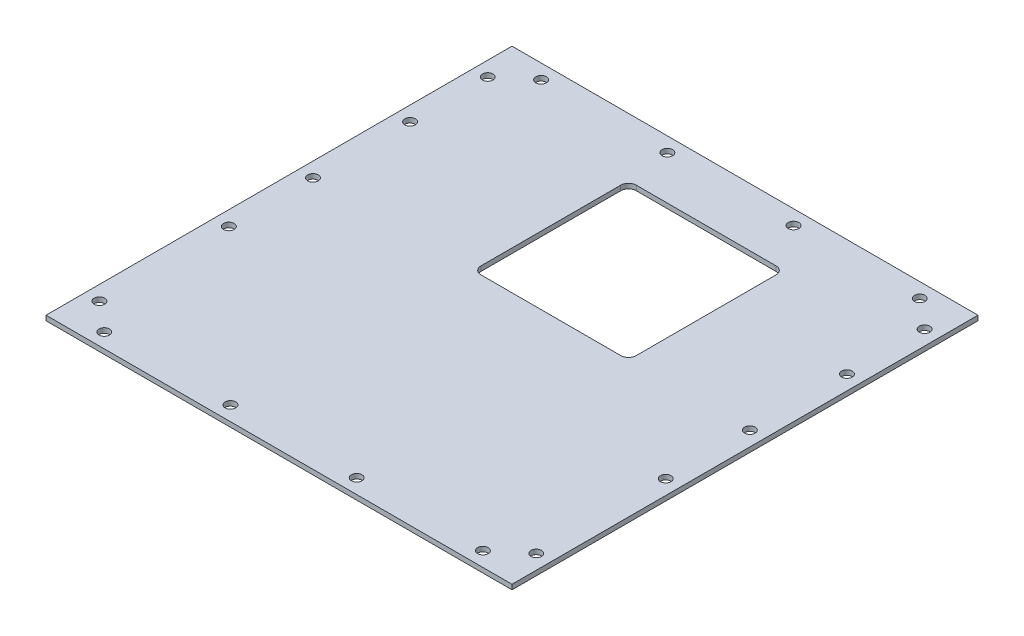
SolidWorks part; units mm, degrees
ref_plane "Front Plane" through (0, 0, 0) normal (0, 0, 1) x (1, 0, 0)
ref_plane "Top Plane" through (0, 0, 0) normal (0, 1, 0) x (1, 0, 0)
ref_plane "Right Plane" through (0, 0, 0) normal (1, 0, 0) x (0, 0, -1)
sketch "Sketch2" plane through (0, 0, 0) normal (0, 1, 0) x (1, 0, 0)
  line L0 (0, 0) -> (152.4, 0)
  line L1 (152.4, 0) -> (152.4, 152.4)
  line L2 (152.4, 152.4) -> (0, 152.4)
  line L3 (0, 152.4) -> (0, 0)
  dimension "D1" = 152.4
  dimension "D2" = 152.4
extrude "Boss-Extrude1" add sketch "Sketch2" along normal blind 1.5875
sketch "Sketch3" plane through (0, 1.5875, 0) normal (0, 1, 0) x (1, 0, 0)
  line L0 (0, 152.4) -> (4.7625, 152.4)
  line L1 (152.4, 152.4) -> (0, 152.4) construction
  line L2 (4.7625, 152.4) -> (4.7625, 0)
  line L3 (0, 0) -> (152.4, 0) construction
  line L4 (0, 152.4) -> (0, 147.6375)
  line L5 (0, 152.4) -> (0, 0) construction
  line L6 (0, 147.6375) -> (152.4, 147.6375)
  line L7 (152.4, 0) -> (152.4, 152.4) construction
  line L8 (152.4, 152.4) -> (147.6375, 152.4)
  line L9 (147.6375, 152.4) -> (147.6375, 0)
  line L10 (152.4, 0) -> (152.4, 4.7625)
  line L11 (152.4, 4.7625) -> (0, 4.7625)
  point P21 (4.7625, 139.7)
  point P23 (14.2875, 147.6375)
  point P24 (147.6375, 139.7)
  point P25 (138.1125, 4.7625)
  point P26 (4.7625, 12.7)
  dimension "D1" = 4.7625
  dimension "D2" = 4.7625
  dimension "D3" = 4.7625
  dimension "D4" = 4.7625
  dimension "D5" = 12.7
  dimension "D6" = 14.2875
  dimension "D7" = 12.7
  dimension "D8" = 14.2875
  dimension "D9" = 12.7
sketch "Sketch4" plane through (0, 1.5875, 0) normal (0, 1, 0) x (1, 0, 0)
  point P0 (14.2875, 147.6375)
  point P3 (147.6375, 139.7)
  point P6 (138.1125, 4.7625)
  point P9 (4.7625, 12.7)
sketch "Sketch6" plane through (0, 1.5875, 0) normal (0, 1, 0) x (1, 0, 0)
  line L0 (152.4, 4.7625) -> (0, 4.7625) construction
  line L1 (0, 152.4) -> (0, 0) construction
  point P0 (14.2875, 147.6375)
  point P3 (14.2875, 4.7625)
  dimension "D1" = 14.2875
hole_wizard "#5 Clearance Hole2" positions "Sketch6" profile "Sketch7" hole size "#5" standard "ANSI Inch" end condition through all
sketch "Sketch7" plane through (14.2875, 1.5875, -147.6375) normal (1, 0, 0) x (0, 0, 1)
  line L0 (0, 0) -> (0, 1.5875)
  line L1 (0, 1.5875) -> (1.7272, 1.5875)
  line L2 (1.7272, 1.5875) -> (1.7272, 0)
  line L5 (1.7272, 0) -> (0, 0)
  line L11 (0, -6.35) -> (0, 107.95) construction
  dimension "Thru Hole Dia." = 3.4544
  dimension "Thru Hole Depth" = 1.5875
sketch "Sketch8" plane through (0, 1.5875, 0) normal (0, 1, 0) x (1, 0, 0)
  point P0 (4.7625, 139.7)
  point P3 (147.6375, 139.7)
hole_wizard "#5 Clearance Hole3" positions "Sketch8" profile "Sketch9" hole size "#5" standard "ANSI Inch" end condition through all
sketch "Sketch9" plane through (4.7625, 1.5875, -139.7) normal (1, 0, 0) x (0, 0, 1)
  line L0 (0, 0) -> (0, 1.5875)
  line L1 (0, 1.5875) -> (1.7272, 1.5875)
  line L2 (1.7272, 1.5875) -> (1.7272, 0)
  line L5 (1.7272, 0) -> (0, 0)
  line L11 (0, -6.35) -> (0, 107.95) construction
  dimension "Thru Hole Dia." = 3.4544
  dimension "Thru Hole Depth" = 1.5875
pattern_linear "LPattern1" count 4 spacing 42.3333 along (0, 0, 1) skipping (1, 0) of "#5 Clearance Hole3"
pattern_linear "LPattern2" count 4 spacing 41.275 along (1, 0, 0) of "#5 Clearance Hole2"
sketch "Sketch10" plane through (0, 1.5875, 0) normal (0, 1, 0) x (1, 0, 0)
  line L0 (152.4, 0) -> (152.4, 152.4) construction
  line L1 (152.4, 152.4) -> (0, 152.4) construction
  line L2 (76.2, 152.4) -> (76.2, 0) construction
  line L3 (0, 0) -> (152.4, 0) construction
  point P0 (147.6375, 114.3)
  point P5 (147.6375, 82.55)
  point P10 (4.7625, 82.55)
  point P11 (4.7625, 114.3)
  dimension "D1" = 4.7625
  dimension "D2" = 38.1
  dimension "D3" = 31.75
hole_wizard "#5 Clearance Hole4" positions "Sketch10" profile "Sketch11" hole size "#5" standard "ANSI Inch"
sketch "Sketch11" plane through (147.6375, 1.5875, -114.3) normal (1, 0, 0) x (0, 0, 1)
  line L0 (0, 0) -> (0, 13.7378)
  line L1 (0, 13.7378) -> (1.7272, 12.7)
  line L2 (1.7272, 12.7) -> (1.7272, 0)
  line L5 (1.7272, 0) -> (0, 0)
  line L10 (0, 13.7378) -> (-1.7272, 12.7) construction
  line L11 (0, -6.35) -> (0, 107.95) construction
  dimension "Hole Dia." = 3.4544
  dimension "Hole Depth" = 12.7
  dimension "Drill Angle" = 118
sketch "Sketch12" plane through (0, 1.5875, 0) normal (0, 1, 0) x (1, 0, 0)
  line L10 (0, 152.4) -> (0, 0) construction
  line L11 (57.15, 133.35) -> (107.95, 133.35)
  line L12 (57.15, 133.35) -> (57.15, 82.55)
  line L13 (57.15, 82.55) -> (107.95, 82.55)
  line L14 (107.95, 133.35) -> (107.95, 82.55)
  line L15 (152.4, 152.4) -> (0, 152.4) construction
  line L16 (152.4, 0) -> (152.4, 152.4) construction
  dimension "D1" = 57.15
  dimension "D2" = 19.05
  dimension "D3" = 44.45
  dimension "D4" = 50.8
extrude "Cut-Extrude1" cut sketch "Sketch12" against normal blind 2.54 contours L14 L12 region at (82.55, 1.5875, -107.95)
fillet "Fillet2" radius 2.54 4 edges at (107.95, 0.7937, -82.55) (57.15, 0.7937, -82.55) (57.15, 0.7937, -133.35) (107.95, 0.7937, -133.35)
